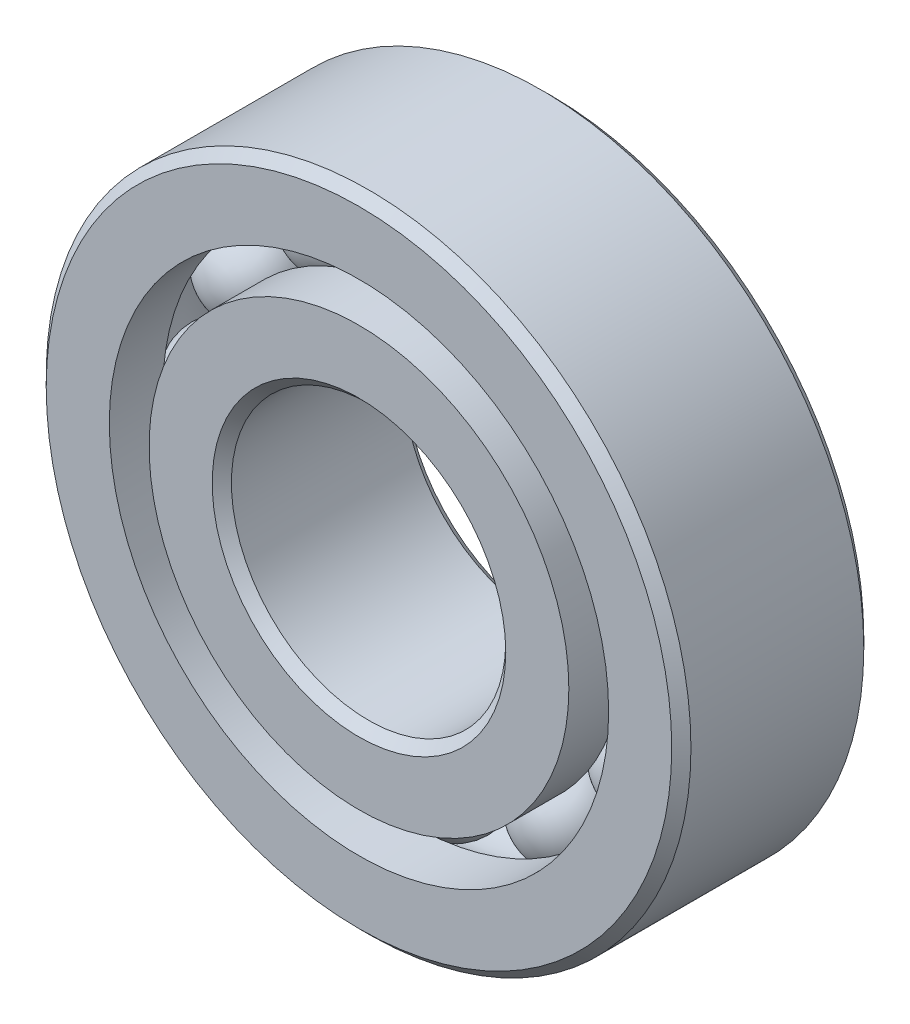
SolidWorks part; units mm, degrees
material "合金钢"
ref_plane "Front Plane" through (0, 0, 0) normal (0, 0, 1) x (1, 0, 0)
ref_plane "Top Plane" through (0, 0, 0) normal (0, 1, 0) x (1, 0, 0)
ref_plane "Right Plane" through (0, 0, 0) normal (1, 0, 0) x (0, 0, -1)
sketch "Sketch1" plane through (0, 0, 0) normal (1, 0, 0) x (0, 0, -1)
  line L0 (-7, 0) -> (7, 0) construction
  line L1 (0, 23.5) -> (0, -23.5) construction
  line L2 (6.3, 23.5) -> (-6.3, 23.5)
  line L3 (-6.3, 23.5) -> (-7, 22.8)
  line L4 (-7, 22.8) -> (-7, 18.2005)
  line L5 (-7, 18.2005) -> (-3.1111, 18.2005)
  line L6 (7, 18.2005) -> (3.1111, 18.2005)
  line L7 (7, 22.8) -> (7, 18.2005)
  line L8 (6.3, 23.5) -> (7, 22.8)
  line L9 (0, 23.5) -> (0, 16.75) construction
  line L10 (0, 16.75) -> (0, 10) construction
  arc A0 (-3.1111, 18.2005) -> (3.1111, 18.2005) centre (0, 16.75) cw
  point P14 (0, 10)
  dimension "Width" = 14
  dimension "OD" = 47
  dimension "D1" = 45
  dimension "D2" = 0.7
  dimension "Shaft Dia" = 20
  dimension "D3" = 6.2222
  dimension "D4" = 1.4505
revolve "Revolve1" add sketch "Sketch1" angle 360 about L0
sketch "Sketch3" plane through (0, 0, 0) normal (1, 0, 0) x (0, 0, -1)
  line L0 (-7, 15.2995) -> (-3.1111, 15.2995)
  line L1 (0, 23.5) -> (0, -23.5) construction
  line L2 (-7, 22.8) -> (-7, 18.2005) construction
  line L3 (-7, 15.2995) -> (-7, 10.7)
  line L4 (-6.3, 23.5) -> (-7, 22.8) construction
  line L5 (-7, 10.7) -> (-6.3, 10)
  line L6 (-6.3, 10) -> (6.3, 10)
  line L7 (6.3, 23.5) -> (6.3, -23.5) construction
  line L8 (6.3, 10) -> (7, 10.7)
  line L9 (7, -22.8) -> (7, 22.8) construction
  line L10 (7, 10.7) -> (7, 15.2995)
  line L11 (7, 15.2995) -> (3.1111, 15.2995)
  line L13 (6.3, 23.5) -> (7, 22.8) construction
  arc A0 (3.1111, 18.2005) -> (-3.1111, 18.2005) centre (0, 16.75) ccw construction
  arc A1 (3.1111, 15.2995) -> (-3.1111, 15.2995) centre (0, 16.75) cw
revolve "Revolve3" add sketch "Sketch3" angle 360 about L0
sketch "Sketch4" plane through (0, 0, 0) normal (1, 0, 0) x (0, 0, -1)
  line L0 (-3.4327, 16.75) -> (3.4327, 16.75)
  arc A2 (-3.4327, 16.75) -> (3.4327, 16.75) centre (0, 16.75) cw
  arc A3 (3.1111, 18.2005) -> (-3.1111, 18.2005) centre (0, 16.75) ccw construction
revolve "Revolve4" add sketch "Sketch4" angle 360 about L0
ref_axis "Axis1" through (0, 0, -7) along (0, 0, 1)
pattern_circular "CirPattern1" count 12 every 30 about axis through (0, 0, -7) along (0, 0, 1) of bodies 104
sketch "Sketch5" plane through (0, 0, 0) normal (1, 0, 0) x (0, 0, -1)
  line L0 (-7, 18.2005) -> (-3.1111, 18.2005) construction
  line L1 (-6.65, 18.2005) -> (-3.4327, 18.2005)
  line L2 (-6.65, 18.2005) -> (-6.65, 15.2995)
  line L3 (-6.65, 15.2995) -> (-3.4327, 15.2995)
  line L4 (-3.4327, 18.2005) -> (-3.4327, 15.2995)
  line L5 (-7, 15.2995) -> (-3.1111, 15.2995) construction
  line L6 (7, 18.2005) -> (3.1111, 18.2005) construction
  line L7 (6.65, 18.2005) -> (3.4327, 18.2005)
  line L8 (6.65, 18.2005) -> (6.65, 15.2995)
  line L9 (6.65, 15.2995) -> (3.4327, 15.2995)
  line L10 (3.4327, 18.2005) -> (3.4327, 15.2995)
  line L11 (7, 15.2995) -> (3.1111, 15.2995) construction
  line L12 (-6.3, 23.5) -> (-7, 22.8) construction
  point P18 (-6.65, 23.15)
equation "\"D2@Sketch1\" = \"Width@Sketch1\"*.05"
equation "\"D3@Sketch1\" = \"Width@Sketch1\"/2.25"
equation "\"D4@Sketch1\" = (((\"OD@Sketch1\"-\"Width@Sketch1\")/2)/3.25)/3.5"
equation "\"D2@CirPattern1\" = 360/\"Balls@CirPattern1\""
